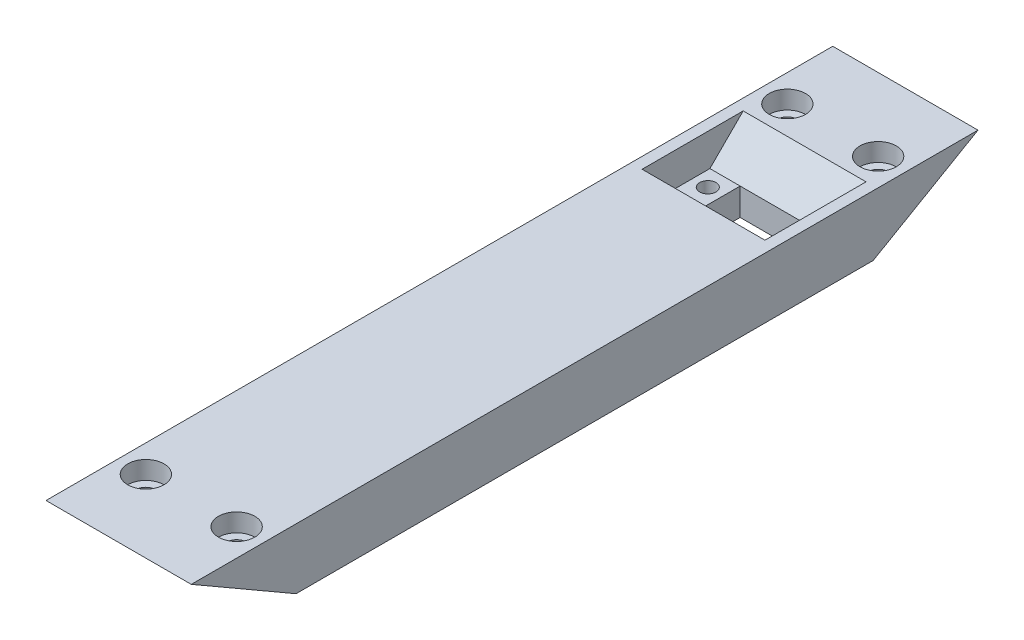
SolidWorks part; units mm, degrees
material "ABS"
ref_plane "Front Plane" through (0, 0, 0) normal (0, 0, 1) x (1, 0, 0)
ref_plane "Top Plane" through (0, 0, 0) normal (0, 1, 0) x (1, 0, 0)
ref_plane "Right Plane" through (0, 0, 0) normal (1, 0, 0) x (0, 0, -1)
sketch "Sketch1" plane through (0, 0, 0) normal (1, 0, 0) x (0, 0, -1)
  line L0 (-65, 0) -> (65, 0)
  line L1 (65, 0) -> (47.6795, -10)
  line L2 (47.6795, -10) -> (-47.6795, -10)
  line L3 (-47.6795, -10) -> (-65, 0)
  point P4 (0, 0)
  dimension "D1" = 30
  dimension "D2" = 130
  dimension "D3" = 10
extrude "Boss-Extrude1" add sketch "Sketch1" along normal mid plane 24
sketch "Sketch2" plane through (0, 0, 0) normal (0, 1, 0) x (1, 0, 0)
  line L1 (-10.15, 37.15) -> (10.15, 37.15)
  line L2 (-10.15, 37.15) -> (-10.15, 42.85)
  line L3 (-10.15, 42.85) -> (10.15, 42.85)
  line L4 (10.15, 37.15) -> (10.15, 42.85)
  line L5 (-10.15, 37.15) -> (10.15, 42.85) construction
  line L6 (-10.15, 42.85) -> (10.15, 37.15) construction
  point P0 (0, 40)
  dimension "D1" = 40
  dimension "D2" = 20.3
  dimension "D3" = 5.7
extrude "Cut-Extrude1" cut sketch "Sketch2" against normal blind 5.5 and the other way through all
sketch "Sketch3" plane through (0, -5.5, 0) normal (0, 1, 0) x (1, 0, 0)
  line L0 (-10.15, 37.15) -> (10.15, 37.15) construction
  line L1 (-10.15, 42.85) -> (-5.15, 42.85)
  line L2 (-10.15, 42.85) -> (-10.15, 37.15)
  line L3 (-10.15, 37.15) -> (-5.15, 37.15)
  line L4 (-5.15, 42.85) -> (-5.15, 37.15)
  line L5 (10.15, 42.85) -> (-10.15, 42.85) construction
  line L6 (10.15, 37.15) -> (5.15, 37.15)
  line L7 (10.15, 37.15) -> (10.15, 42.85)
  line L8 (10.15, 42.85) -> (5.15, 42.85)
  line L9 (5.15, 37.15) -> (5.15, 42.85)
  line L10 (-10.15, 42.85) -> (-5.15, 37.15) construction
  line L11 (-5.15, 37.15) -> (5.15, 37.15)
  line L12 (-5.15, 37.15) -> (-5.15, 42.85)
  line L13 (-5.15, 42.85) -> (5.15, 42.85)
  line L14 (5.15, 37.15) -> (5.15, 42.85)
  line L15 (5.15, 37.15) -> (10.15, 42.85) construction
  circle A0 centre (-7.65, 40) radius 1.35
  circle A1 centre (7.65, 40) radius 1.35
  line M15 (10.15, 42.85) -> (-10.15, 42.85)
  line M17 (-10.15, 37.15) -> (10.15, 37.15)
  dimension "D2" = 2.7
  dimension "D1" = 5
extrude "Cut-Extrude2" cut sketch "Sketch3" against normal blind 5.5 contours L9 L4 M17 M15 | A0 | A1 region at (0, -5.5, -40) region at (-7.65, -5.5, -40)
chamfer "Chamfer1" distance 5.5 angle 45 2 edges at (0, 0, -37.15) (0, 0, -42.85)
sketch "Sketch4" plane through (0, 0, 0) normal (0, 1, 0) x (1, 0, 0)
  line L0 (-7.5, 53) -> (7.5, 53) construction
  circle A0 centre (-7.5, 53) radius 1.625
  circle A1 centre (7.5, 53) radius 1.625
  point P4 (0, 53)
  dimension "D1" = 3.25
  dimension "D2" = 53
  dimension "D3" = 15
extrude "Cut-Extrude3" cut sketch "Sketch4" against normal through all
sketch "Sketch5" plane through (0, 0, 0) normal (0, 1, 0) x (1, 0, 0)
  circle A0 centre (-7.5, 53) radius 3
  circle A1 centre (7.5, 53) radius 3
  circle A2 centre (7.5, 53) radius 1.625 construction
  dimension "D1" = 6
extrude "Cut-Extrude4" cut sketch "Sketch5" against normal blind 3
mirror "Mirror1" about plane through (0, 0, 0) normal (0, 0, 1) of "Cut-Extrude4", "Cut-Extrude3"
